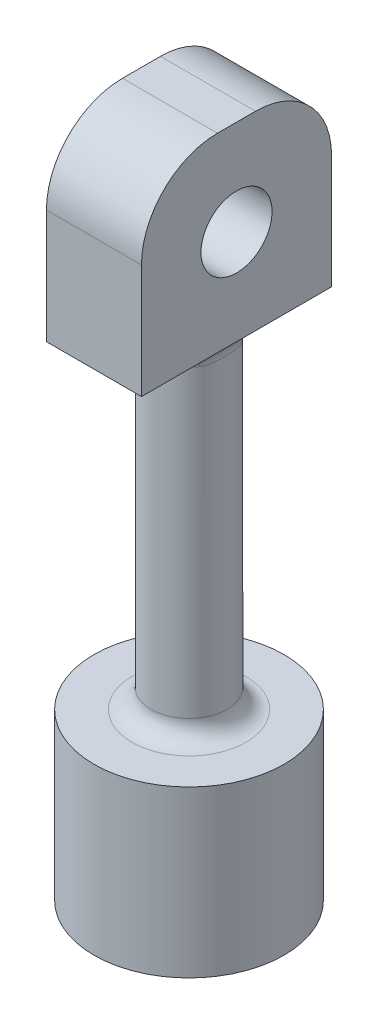
SolidWorks part; units mm, degrees
ref_plane "Front Plane" through (0, 0, 0) normal (0, 0, 1) x (1, 0, 0)
ref_plane "Top Plane" through (0, 0, 0) normal (0, 1, 0) x (1, 0, 0)
ref_plane "Right Plane" through (0, 0, 0) normal (1, 0, 0) x (0, 0, -1)
sketch "Sketch1" plane through (0, 0, 0) normal (0, 0, 1) x (1, 0, 0)
  line L0 (0, 1403.1859) -> (0, -1415.2336) construction
  line L1 (0, -6.0239) -> (250, -6.0239)
  line L2 (250, -6.0239) -> (250, 428.9761)
  line L3 (250, 428.9761) -> (150, 428.9761)
  line L4 (100, 478.9761) -> (100, 1328.9761)
  line L5 (100, 1328.9761) -> (0, 1328.9761)
  line L6 (0, 1328.9761) -> (0, -6.0239)
  arc A0 (150, 428.9761) -> (100, 478.9761) centre (150, 478.9761) cw
  dimension "D1" = 50
  dimension "D2" = 100
revolve "Revolve1" add sketch "Sketch1" angle 360 about L6
sketch "Sketch2" plane through (0, 1328.9761, 0) normal (0, 1, 0) x (1, 0, 0)
  line L1 (125, -250) -> (-125, -250)
  line L2 (125, -250) -> (125, 250)
  line L3 (125, 250) -> (-125, 250)
  line L4 (-125, -250) -> (-125, 250)
  line L5 (125, -250) -> (-125, 250) construction
  line L6 (125, 250) -> (-125, -250) construction
  point P0 (0, 0)
  dimension "D1" = 250
  dimension "D2" = 500
extrude "Boss-Extrude1" add sketch "Sketch2" along normal blind 500
fillet "Fillet1" radius 200 2 edges at (0, 1828.9761, -250) (0, 1828.9761, 250)
sketch "Sketch3" plane through (-125, 0, 0) normal (-1, 0, 0) x (0, 0, 1)
  line L0 (0, 1328.9761) -> (0, 1828.9761) construction
  line L1 (-250, 1328.9761) -> (250, 1328.9761) construction
  line L2 (-50, 1828.9761) -> (50, 1828.9761) construction
  circle A0 centre (0, 1578.9761) radius 93.5
extrude "Cut-Extrude1" cut sketch "Sketch3" against normal up to next
fillet "Fillet2" radius 50 1 edges at (0, 1328.9761, 100)
